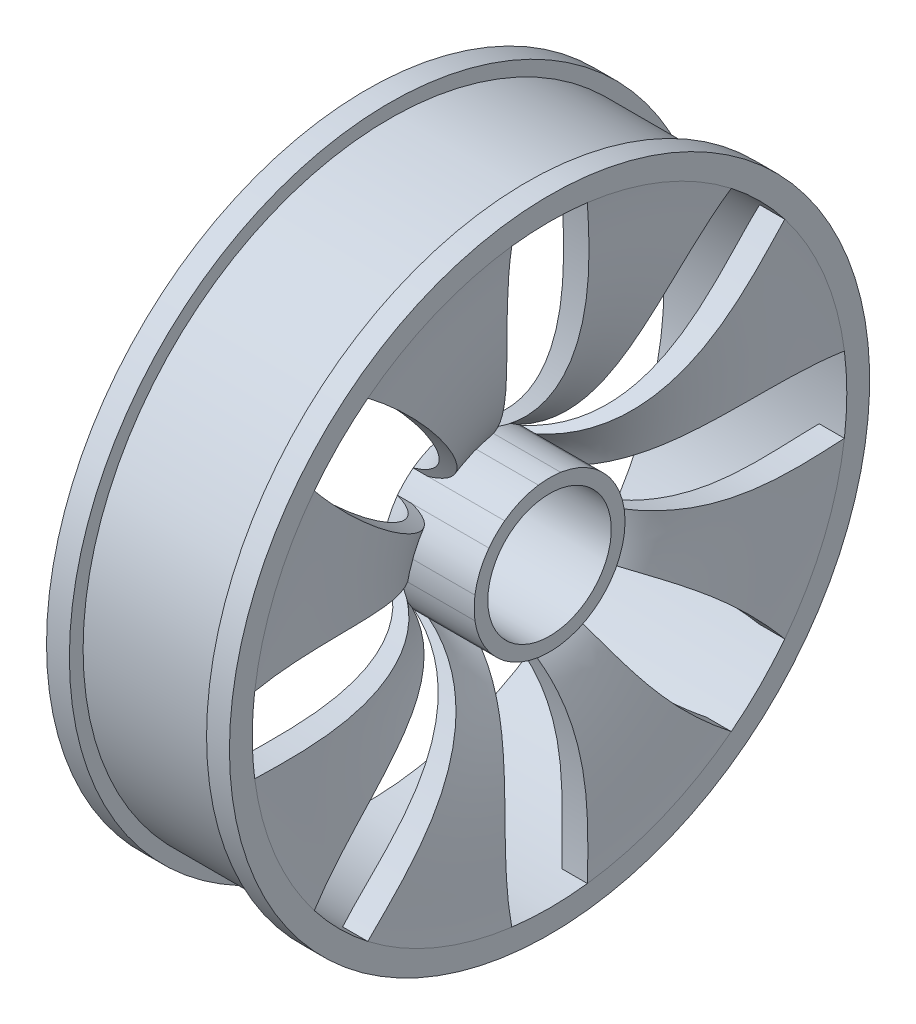
SolidWorks part; units mm, degrees
ref_plane "Front Plane" through (0, 0, 0) normal (0, 0, 1) x (1, 0, 0)
ref_plane "Top Plane" through (0, 0, 0) normal (0, 1, 0) x (1, 0, 0)
ref_plane "Right Plane" through (0, 0, 0) normal (1, 0, 0) x (0, 0, -1)
sketch "Sketch1" plane through (0, 0, 0) normal (0, 0, 1) x (1, 0, 0)
  line L0 (0, 0) -> (83.9712, 0) construction
  line L1 (-20, 65) -> (13.1537, 65)
  line L2 (20, 65) -> (20, 70)
  line L3 (20, 70) -> (15, 70)
  line L4 (15, 70) -> (15, 67)
  line L5 (15, 67) -> (-15, 67)
  line L7 (0, 0) -> (0, 21.9627) construction
  line L8 (-15, 70) -> (-15, 67)
  line L9 (-20, 70) -> (-15, 70)
  line L10 (-20, 65) -> (-20, 70)
  line L17 (13.1537, 65) -> (14.4947, 65)
  line L18 (0, 13.5) -> (20, 13.5)
  line L19 (20, 13.5) -> (20, 16.5)
  line L20 (20, 16.5) -> (3.1757, 16.5)
  line L21 (0, 16.5) -> (0, 13.5)
  spline S0 degree 3 poles (20, 65) (18.8064, 48.991) (21.6541, 24.8964) (3.1757, 16.5) knots 0 0 0 0 1 1 1 1
  spline S1 degree 3 poles (14.4947, 65) (12.5022, 49.4908) (18.4668, 25.2484) (0, 16.5) knots 0 0 0 0 1 1 1 1
  dimension "D1" = 40
  dimension "D2" = 30
  dimension "D3" = 3
  dimension "D4" = 67
  dimension "D5" = 2
  dimension "D7" = 3
  dimension "D6" = 20
  dimension "D8" = 13.5
revolve "Revolve1" add sketch "Sketch1" angle 360 about L0
ref_plane "Plane1" through (30, 0, 0) normal (1, 0, 0) x (0, 0, -1)
sketch "Sketch2" plane through (30, 0, 0) normal (1, 0, 0) x (0, 0, -1)
  circle A12 centre (0, 0) radius 65 construction
  circle A13 centre (0, 0) radius 16.5 construction
  circle A14 centre (0, 0) radius 16.5 construction
  arc A15 (-8.2695, 64.4718) -> (8.2695, 64.4718) centre (0, 0) cw
  arc A16 (-2.435, 16.3193) -> (2.435, 16.3193) centre (0, -1.5152) cw
  spline S0 degree 2 poles (-8.2695, 64.4718) (-10.5417, 39.8353) (-2.435, 16.3193) knots 0 0 0 1 1 1
  spline S1 degree 2 poles (8.2695, 64.4718) (11.4096, 39.7562) (2.435, 16.3193) knots 0 0 0 1 1 1
extrude "Cut-Extrude2" cut sketch "Sketch2" against normal through all
pattern_circular "CirPattern2" count 8 over 360 about axis through (20, 0, 0) along (-1, 0, 0) of "Cut-Extrude2"
